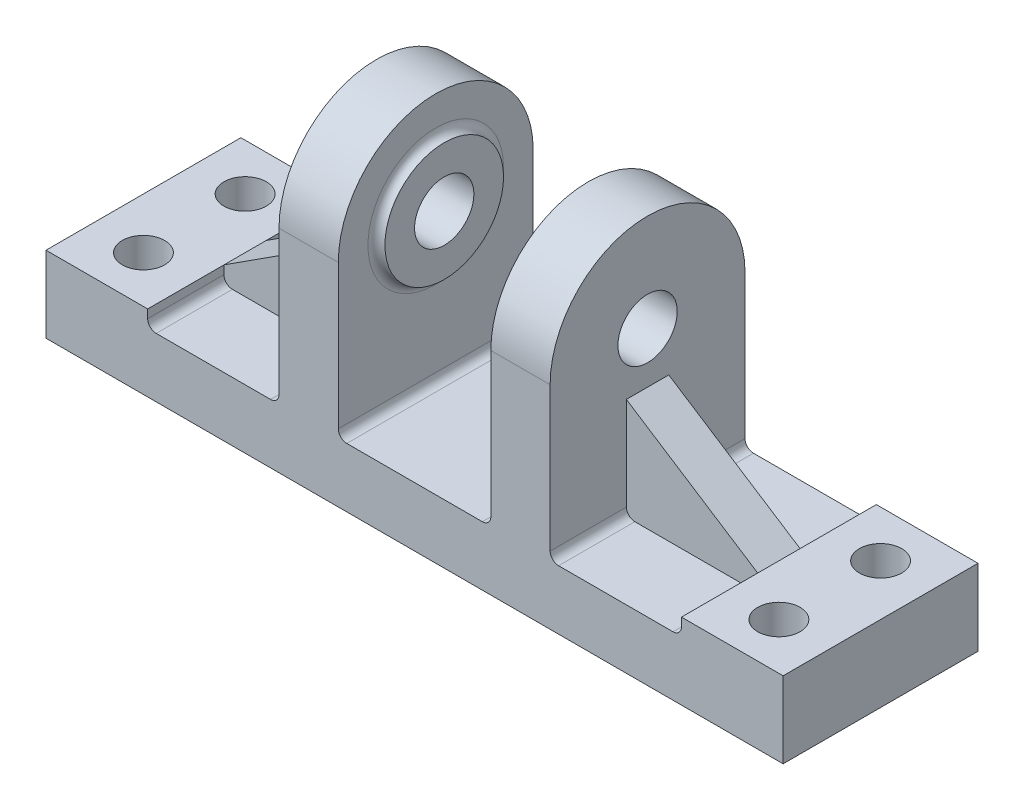
SolidWorks part; units mm, degrees
ref_plane "Front Plane" through (0, 0, 0) normal (0, 0, 1) x (1, 0, 0)
ref_plane "Top Plane" through (0, 0, 0) normal (0, 1, 0) x (1, 0, 0)
ref_plane "Right Plane" through (0, 0, 0) normal (1, 0, 0) x (0, 0, -1)
sketch "Sketch1" plane through (0, 0, 0) normal (0, 0, 1) x (1, 0, 0)
  line L1 (-32.8739, 18) -> (141.1261, 18)
  line L2 (-32.8739, 18) -> (-32.8739, 0)
  line L3 (-32.8739, 0) -> (141.1261, 0)
  line L4 (141.1261, 18) -> (141.1261, 0)
  dimension "D1" = 18
  dimension "D2" = 174
extrude "Boss-Extrude1" add sketch "Sketch1" against normal blind 46
sketch "Sketch3" plane through (0, 18, 0) normal (0, 1, 0) x (1, 0, 0)
  line L0 (141.1261, 46) -> (-32.8739, 46) construction
  line L1 (-8.8739, 46) -> (117.1261, 46)
  line L2 (-8.8739, 46) -> (-8.8739, 0)
  line L3 (-8.8739, 0) -> (117.1261, 0)
  line L4 (117.1261, 46) -> (117.1261, 0)
  line L5 (141.1261, 0) -> (-32.8739, 0) construction
  line L6 (141.1261, 46) -> (141.1261, 0) construction
  line L7 (-32.8739, 46) -> (-32.8739, 0) construction
  dimension "D1" = 24
  dimension "D2" = 24
extrude "Cut-Extrude1" cut sketch "Sketch3" against normal blind 4
ref_plane "Plane1" through (86.1261, 0, 0) normal (1, 0, 0) x (0, 0, -1)
sketch "Sketch4" plane through (86.1261, 0, 0) normal (1, 0, 0) x (0, 0, -1)
  line L0 (46, 14) -> (0, 14)
  line L1 (0, 14) -> (0, 50)
  line L2 (46, 50) -> (46, 14)
  line L3 (46, 0) -> (0, 0) construction
  arc A0 (0, 50) -> (46, 50) centre (23, 50) cw
  circle A1 centre (23, 50) radius 7
  point P9 (23, 0)
  dimension "D1" = 14
  dimension "D2" = 50
extrude "Boss-Extrude2" add sketch "Sketch4" against normal blind 14
sketch "Sketch5" plane through (72.1261, 0, 0) normal (-1, 0, 0) x (0, 0, 1)
  circle A0 centre (-23, 50) radius 14
  circle A2 centre (-23, 50) radius 7 construction
  circle A3 centre (-23, 50) radius 7
  dimension "D1" = 28
extrude "Boss-Extrude3" add sketch "Sketch5" along normal blind 2
ref_plane "Plane2" through (0, 0, -23) normal (0, 0, 1) x (1, 0, 0)
sketch "Sketch6" plane through (0, 0, -23) normal (0, 0, 1) x (1, 0, 0)
  line L0 (117.1261, 18) -> (86.1261, 38)
  line L1 (86.1261, 50) -> (86.1261, 14) construction
  dimension "D1" = 12
rib "Rib1" sketch "Sketch6" sketch "Sketch6" thickness 10 extrusion direction parallel to sketch draft on no parameters "D1"=10
ref_plane "Plane3" through (54.1261, 0, 0) normal (1, 0, 0) x (0, 0, -1)
mirror "Mirror4" about plane through (54.1261, 0, 0) normal (1, 0, 0) of bodies 104
fillet "Fillet1" radius 2 10 edges at (-8.8739, 14, -9) (86.1261, 14, -9) (86.1261, 14, -37) (36.1261, 14, -23) (-8.8739, 14, -37) (22.1261, 14, -37) (22.1261, 14, -9) (72.1261, 14, -23) (117.1261, 14, -9) (117.1261, 14, -37)
fillet "Fillet2" radius 2 1 edges at (36.1261, 50, -9)
fillet "Fillet3" radius 2 1 edges at (72.1261, 50, -9)
hole_wizard "Ø10.0 (10) Diameter Hole5" positions "Sketch19" profile "Sketch18" hole size "Ø10.0" standard "DIN" end condition through all
sketch "Sketch19" plane through (0, 18, 0) normal (0, 1, 0) x (1, 0, 0)
  line L0 (141.1261, 46) -> (141.1261, 0) construction
  line L2 (54.1261, -9.9) -> (54.1261, 9.9) construction
  point P0 (-20.8739, 35)
  point P2 (-20.8739, 11)
  point P4 (129.1261, 35)
  point P6 (129.1261, 11)
  point P7 (141.1261, 23)
  dimension "D1" = 150
  dimension "D2" = 24
  dimension "D3" = 12
  dimension "D4" = 75
sketch "Sketch18" plane through (-20.8739, 18, -35) normal (1, 0, 0) x (0, 0, 1)
  line L0 (0, 0) -> (0, 18)
  line L1 (0, 18) -> (5, 18)
  line L2 (5, 18) -> (5, 0)
  line L5 (5, 0) -> (0, 0)
  line L11 (0, -6.35) -> (0, 107.95) construction
  dimension "Thru Hole Dia." = 10
  dimension "Thru Hole Depth" = 18
